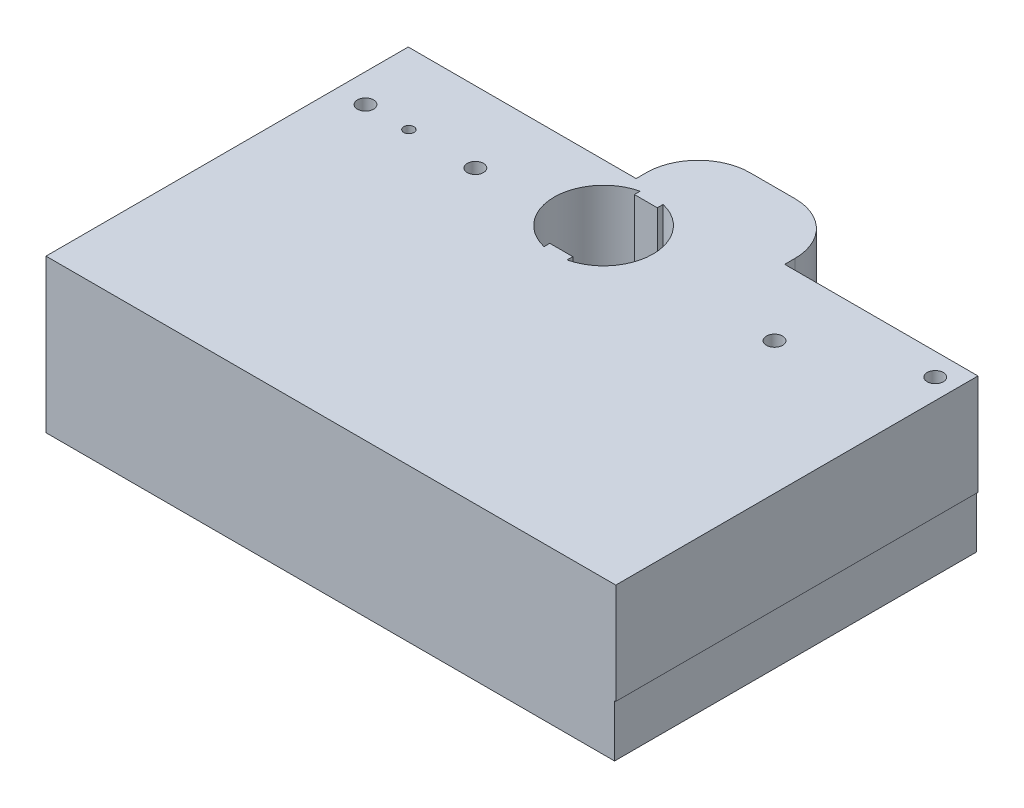
SolidWorks part; units mm, degrees
ref_plane "Front Plane" through (0, 0, 0) normal (0, 0, 1) x (1, 0, 0)
ref_plane "Top Plane" through (0, 0, 0) normal (0, 1, 0) x (1, 0, 0)
ref_plane "Right Plane" through (0, 0, 0) normal (1, 0, 0) x (0, 0, -1)
sketch "Sketch1" plane through (0, 0, 0) normal (0, 1, 0) x (1, 0, 0)
  line L1 (0, 0) -> (279.4, 0)
  line L2 (0, 0) -> (0, 177.8)
  line L3 (0, 177.8) -> (279.4, 177.8)
  line L4 (279.4, 0) -> (279.4, 177.8)
  dimension "D1" = 279.4
  dimension "D2" = 177.8
extrude "Boss-Extrude1" add sketch "Sketch1" along normal blind 25.654
sketch "Sketch9" plane through (0, 25.654, 0) normal (0, 1, 0) x (1, 0, 0)
  line L0 (129.6393, 129.22) -> (129.6393, 126.384)
  line L1 (118.3607, 129.22) -> (129.6393, 129.22)
  line L2 (118.3607, 129.22) -> (118.3607, 126.384)
  line L3 (118.3607, 173.616) -> (118.3607, 170.78)
  line L4 (118.3607, 170.78) -> (129.6393, 170.78)
  line L5 (129.6393, 173.616) -> (129.6393, 170.78)
  line L6 (0, 108) -> (127.6, 108)
  line L7 (127.6, 0) -> (127.6, 108)
  line L8 (127.6, 0) -> (280, 0)
  line L9 (280, 0) -> (280, 178)
  line L10 (0, 178) -> (280, 178)
  line L11 (0, 108) -> (0, 178)
  line L12 (279.4, 0) -> (279.4, 177.8) construction
  arc A0 (118.3607, 173.616) -> (118.3607, 126.384) centre (124, 150) ccw
  arc A1 (129.6393, 126.384) -> (129.6393, 173.616) centre (124, 150) ccw
  circle A2 centre (35.3189, 143) radius 2.5
  circle A3 centre (14, 143) radius 3.9687
  circle A4 centre (68, 143) radius 3.9688
  circle A6 centre (270, 167) radius 3.9688
  circle A7 centre (215, 143) radius 3.9687
  point P0 (0, 0)
  dimension "D4" = 7.9375
  dimension "D5" = 5
  dimension "D6" = 24.28
  dimension "D7" = 11.2786
  dimension "D21" = 9.4
  dimension "D23" = 65
  dimension "D19" = 7.9375
  dimension "D1" = 280
  dimension "D2" = 178
  dimension "D3" = 70
  dimension "D8" = 124
  dimension "D9" = 35.3189
  dimension "D10" = 14
  dimension "D11" = 68
  dimension "D12" = 35
  dimension "D13" = 35
  dimension "D14" = 127.6
  dimension "D15" = 35
  dimension "D16" = 2.836
  dimension "D17" = 28
  dimension "D18" = 35
  dimension "D20" = 11
extrude "Cut-Extrude1" cut sketch "Sketch9" against normal blind 38.1 contours A7
extrude "Boss-Extrude2" add sketch "Sketch9<7>" along normal blind 49.53
sketch "Sketch9<7>" plane through (0, 25.654, 0) normal (0, 1, 0) x (1, 0, 0) same geometry as "Sketch9"
sketch "Sketch13" plane through (0, 25.654, 0) normal (0, 1, 0) x (1, 0, 0)
  line L1 (0, 108) -> (127.6, 108)
  line L2 (0, 108) -> (0, 0)
  line L3 (0, 0) -> (127.6, 0)
  line L4 (127.6, 108) -> (127.6, 0)
extrude "Boss-Extrude3" add sketch "Sketch13" along normal up to surface (49.53 mm away) contours L2 L1 L4 L3 up to face at (135.8667, 75.184, -95.3333)
sketch "Sketch14" plane through (0, 0, -178) normal (0, 0, -1) x (-1, 0, 0)
  line L0 (-280, 75.184) -> (0, 75.184) construction
  line L1 (-185, 75.184) -> (-112, 75.184)
  line L2 (-185, 75.184) -> (-185, 25.654)
  line L3 (-185, 25.654) -> (-112, 25.654)
  line L4 (-112, 75.184) -> (-112, 25.654)
  line L5 (-280, 25.654) -> (0, 25.654) construction
  line L6 (-280, 75.184) -> (-280, 25.654) construction
  point P10 (-280, 50.419)
  dimension "D1" = 73
  dimension "D3" = 95
extrude "Boss-Extrude4" add sketch "Sketch14" along normal blind 30.48 contours L2 L1 L4 L3
fillet "Fillet1" radius 25.4 1 edges at (185, 50.419, -208.48)
fillet "Fillet2" radius 25.4 1 edges at (112, 50.419, -208.48)
